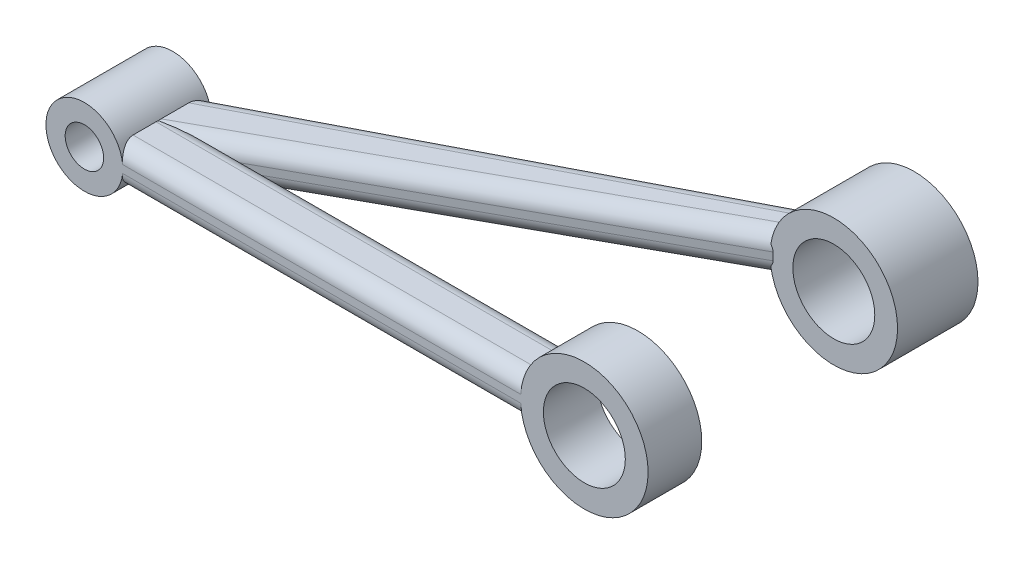
SolidWorks part; units mm, degrees
material "Thornel Mat VMA"
ref_plane "Front Plane" through (0, 0, 0) normal (0, 0, 1) x (1, 0, 0)
ref_plane "Top Plane" through (0, 0, 0) normal (0, 1, 0) x (1, 0, 0)
ref_plane "Right Plane" through (0, 0, 0) normal (1, 0, 0) x (0, 0, -1)
sketch "Sketch1" plane through (0, 0, 0) normal (0, 1, 0) x (1, 0, 0)
  line L0 (-63.9674, -18.9207) -> (66.0326, -18.9207)
  line L1 (66.0326, -18.9207) -> (66.0326, 66.8627)
  line L2 (66.0326, 66.8627) -> (-63.9674, 4.0793)
  line L3 (-63.9674, 4.0793) -> (-63.9674, -18.9207)
extrude "Boss-Extrude1" add sketch "Sketch1" along normal blind 10
sketch "Sketch2" plane through (0, 0, 18.9207) normal (0, 0, 1) x (1, 0, 0)
  line L0 (-63.9674, 10) -> (-63.9674, 0) construction
  circle A0 centre (-63.9674, 5) radius 5
  circle A1 centre (-63.9674, 5) radius 10
extrude "Boss-Extrude2" add sketch "Sketch2" against normal up to vertex (23 mm away) up to point (-63.9674, 0, -4.0793)
sketch "Sketch3" plane through (0, 0, 18.9207) normal (0, 0, 1) x (1, 0, 0)
  line L0 (-63.9674, 10) -> (-63.9674, 0) construction
  circle A0 centre (-63.9674, 5) radius 5
extrude "Cut-Extrude1" cut sketch "Sketch3" against normal blind 27
sketch "Sketch4" plane through (0, 10, 0) normal (0, 1, 0) x (1, 0, 0)
  line L0 (-63.9674, 4.0793) -> (-55.3072, 4.0793)
  line L1 (-55.3072, 4.0793) -> (66.0326, 66.8627)
  line L2 (66.0326, 66.8627) -> (-63.9674, 4.0793)
extrude "Cut-Extrude2" cut sketch "Sketch4" against normal blind 27
sketch "Sketch5" plane through (0, 0, 18.9207) normal (0, 0, 1) x (1, 0, 0)
  line L0 (66.0326, 10) -> (66.0326, 0) construction
  circle A0 centre (66.0326, 5) radius 9.5
  circle A1 centre (66.0326, 5) radius 16.5771
extrude "Boss-Extrude3" add sketch "Sketch5" against normal up to vertex (85.7834 mm away) up to point (66.0326, 10, -66.8627)
sketch "Sketch6" plane through (0, 0, 18.9207) normal (0, 0, 1) x (1, 0, 0)
  line L0 (66.0326, 10) -> (66.0326, 0) construction
  circle A0 centre (66.0326, 5) radius 10.655
  dimension "D1" = 21.31
extrude "Cut-Extrude3" cut sketch "Sketch6" against normal blind 100
sketch "Sketch7" plane through (0, 10, 0) normal (0, 1, 0) x (1, 0, 0)
  line L0 (-42.1947, -4.9673) -> (50.2275, 45.9449)
  line L1 (50.2275, 58.6849) -> (50.2275, -18.9207) construction
  line L2 (50.2275, 45.9449) -> (96.9687, 45.9449)
  line L3 (96.9687, 45.9449) -> (96.9687, -4.9673)
  line L4 (96.9687, -4.9673) -> (-42.1947, -4.9673)
extrude "Cut-Extrude4" cut sketch "Sketch7" against normal blind 49 and the other way blind 18
fillet "Fillet1" radius 4 8 edges at (-2.5398, 0, -31.3821) (-2.5398, 10, -31.3821) (4.0164, 0, -20.4888) (4.0164, 10, -20.4888) (4.0164, 0, 4.9673) (4.0164, 10, 4.9673) (-2.5398, 0, 18.9207) (-2.5398, 10, 18.9207)
